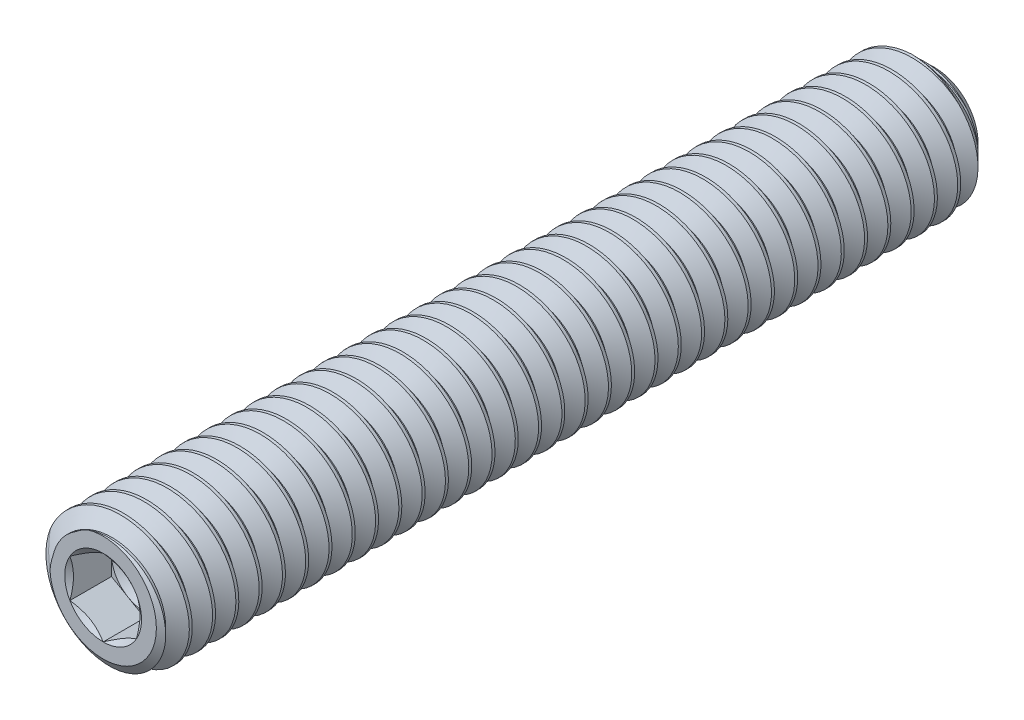
SolidWorks part; units mm, degrees
ref_plane "Front" through (0, 0, 0) normal (0, 0, 1) x (1, 0, 0)
ref_plane "Top" through (0, 0, 0) normal (0, 1, 0) x (1, 0, 0)
ref_plane "Right" through (0, 0, 0) normal (1, 0, 0) x (0, 0, -1)
sketch "Sketch22" plane through (0, 0, 0) normal (1, 0, 0) x (0, 0, -1)
  line L0 (-12.5, 0) -> (-12.5, 1.6)
  line L1 (-12.5, 1.6) -> (-12.2199, 2)
  line L2 (-12.2199, 2) -> (11.8, 2)
  line L3 (11.8, 2) -> (12.5, 1.3)
  line L4 (-0.21, 2) -> (-0.21, -2) construction
  line L5 (12.5, 0) -> (-12.5, 0)
  line L6 (-12.5, 1.6) -> (-12.5, -1.6) construction
  line L7 (12.5, 0) -> (12.5, 1.3)
  point P11 (-0.21, 0)
  dimension "Length" = 25
  dimension "D3" = 35
  dimension "D6" = 45
  dimension "Dia" = 4
  dimension "D1" = 3.2
  dimension "D2" = 0.7
revolve "Revolve1" add sketch "Sketch22" angle 360 about L5
ref_plane "Plane1" through (0, 0, -12.5) normal (0, 0, 1) x (1, 0, 0)
sketch "Sketch27" plane through (0, 0, -12.5) normal (0, 0, 1) x (1, 0, 0)
  circle A0 centre (0, 0) radius 2 construction
  circle A1 centre (0, 0) radius 2
curve "Helix/Spiral1" pitch 0.7 height 25.7 turns 36.7143
sketch "Sketch28" plane through (0, 0, 0) normal (1, 0, 0) x (0, 0, -1)
  line L0 (12.5, 2) -> (13.1125, 2)
  line L1 (13.1125, 2) -> (12.85, 1.5453)
  line L2 (12.85, 1.5453) -> (12.7625, 1.5453)
  line L3 (12.7625, 1.5453) -> (12.5, 2)
  line L4 (12.6312, 1.7727) -> (12.9812, 1.7727) construction
  line L6 (-12.2199, 2) -> (11.8, 2) construction
  dimension "D1" = 0.0875
  dimension "D3" = 60
  dimension "D2" = 0.35
sweep "Cut-Sweep2" cut profiles "Sketch28" path "Helix/Spiral1"
sketch "Sketch23" plane through (0, 0, 12.5) normal (0, 0, 1) x (1, 0, 0)
  line L1 (0, 1.1547) -> (-1, 0.5774)
  line L2 (-1, 0.5774) -> (-1, -0.5774)
  line L3 (-1, -0.5774) -> (0, -1.1547)
  line L4 (0, -1.1547) -> (1, -0.5774)
  line L5 (1, -0.5774) -> (1, 0.5774)
  line L6 (1, 0.5774) -> (0, 1.1547)
  circle A0 centre (0, 0) radius 1 construction
  dimension "Hex" = 2
extrude "Cut-Extrude10" cut sketch "Sketch23" against normal blind 1.25
sketch "Sketch24" plane through (0, 0, 12.5) normal (0, 0, 1) x (1, 0, 0)
  circle A0 centre (0, 0) radius 1.1547
extrude "Cut-Extrude11" cut sketch "Sketch24" against normal through all draft 55
sketch "Sketch26" plane through (0, 0, 11.25) normal (0, 0, 1) x (1, 0, 0)
  circle A0 centre (0, 0) radius 1 construction
  circle A1 centre (0, 0) radius 1
extrude "Cut-Extrude12" cut sketch "Sketch26" against normal through all draft 60
sketch "Sketch30" plane through (0, 0, 0) normal (1, 0, 0) x (0, 0, -1)
  line L0 (-12.2199, 2) -> (11.8, 2) construction
  line L1 (-12.5, 0) -> (-12.5, 1.6) construction
  line L2 (12.5, 0) -> (12.5, 1.3) construction
  point P0 (-12.5, 2)
  point P1 (12.5, 2)
  point P2 (12.5, -2)
  point P11 (10.75, -2)
  dimension "D1" = 1.75
equation "\"D1@Sketch28\" = \"D4@Helix/Spiral1\" * .125"
equation "\"D2@Sketch28\" = \"D4@Helix/Spiral1\" * .5"
equation "\"D3@Helix/Spiral1\" = \"Length@Sketch22\" + \"D4@Helix/Spiral1\""
equation "\"D1@Sketch30\" = \"D4@Helix/Spiral1\" * 2.5"
equation "\"hex Depth@Cut-Extrude10\" = \"Hex@Sketch23\" * .625"
equation "\"D1@Sketch22\" = \"Dia@Sketch22\" * .8"
equation "\"D2@Sketch22\" = \"D4@Helix/Spiral1\""
